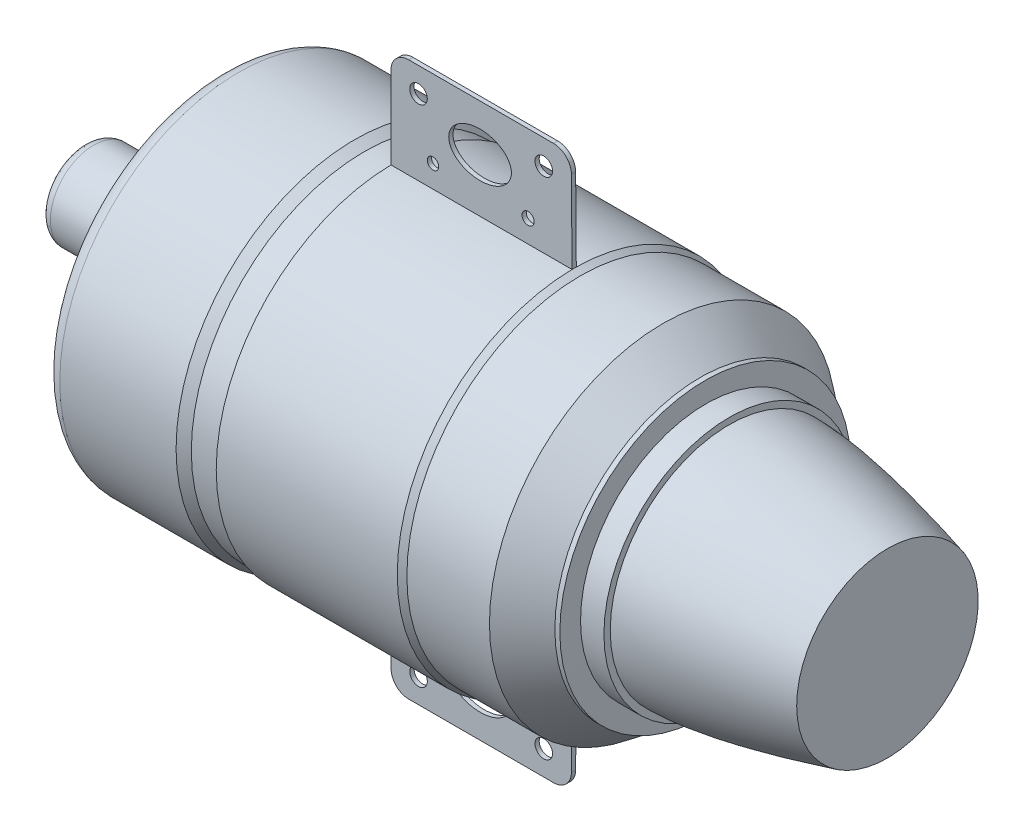
SolidWorks part; units mm, degrees
ref_plane "Front Plane" through (0, 0, 0) normal (0, 0, 1) x (1, 0, 0)
ref_plane "Top Plane" through (0, 0, 0) normal (0, 1, 0) x (1, 0, 0)
ref_plane "Right Plane" through (0, 0, 0) normal (1, 0, 0) x (0, 0, -1)
sketch "Sketch1" plane through (0, 0, 0) normal (0, 0, 1) x (1, 0, 0)
  line L0 (-26.7963, 0) -> (12.4273, 0) construction
  line L1 (1.0905, 5.1722) -> (9.4504, 5.1722)
  line L2 (9.4504, 5.1722) -> (9.4504, 0)
  line L3 (17.0937, 0) -> (17.0937, 18.9133)
  line L4 (19.2083, 21.3115) -> (33.0854, 21.3115)
  line L5 (33.0854, 21.3115) -> (34.2496, 20.6596)
  line L6 (34.2496, 20.6596) -> (37.6708, 20.6596)
  line L7 (59.2694, 21.1075) -> (60.0052, 20.6955)
  line L8 (60.0052, 20.6955) -> (69.8575, 20.6955)
  line L9 (69.8575, 20.6955) -> (74.3124, 17.3492)
  line L10 (74.3124, 17.3492) -> (74.9094, 17.3492)
  line L11 (74.9094, 17.3492) -> (74.9817, 14.9528)
  line L12 (74.9817, 14.9528) -> (77.7707, 14.9528)
  line L13 (77.7707, 14.9528) -> (77.7707, 14.1977)
  line L14 (96.6452, 0) -> (96.6452, 10.8275)
  line L15 (85.173, 14.1977) -> (70.5882, 14.1977) construction
  line L16 (0, 0) -> (0, -2.4925) construction
  line L17 (37.6708, 20.6596) -> (37.6708, 21.1075)
  line L18 (37.6708, 21.1075) -> (59.2694, 21.1075)
  line L19 (17.0937, 17.7576) -> (11.0147, 6.1199)
  line L20 (17.0937, 14.4568) -> (12.1234, 4.9415)
  line L21 (12.1234, 4.9415) -> (12.1234, 0)
  line L22 (37.6708, 21.1075) -> (37.6708, 30.916)
  line L23 (17.0937, 0) -> (96.6452, 0)
  line L24 (39.7842, 33.0294) -> (57.0627, 33.0294)
  line L25 (9.4504, 0) -> (0, 0)
  line L26 (59.1927, 30.916) -> (59.2694, 21.1075)
  line L27 (12.1234, 0) -> (9.4504, 0)
  line L28 (9.4504, 5.1722) -> (9.4504, 7.9511)
  line L29 (9.4504, 7.9511) -> (11.9713, 7.9511)
  line L30 (59.2694, 21.1075) -> (59.2694, 18.6791)
  line L31 (59.2694, 18.6791) -> (37.6708, 18.6791)
  line L32 (37.6708, 18.6791) -> (37.6708, 20.6596)
  arc A0 (17.0937, 18.9133) -> (19.2083, 21.3115) centre (19.511, 18.9133) cw
  arc A1 (0, 0) -> (1.0905, 5.1722) centre (12.8113, 0) cw
  arc A2 (9.4504, 5.1722) -> (11.0147, 6.1199) centre (9.4504, 6.9371) ccw
  arc A3 (37.6708, 30.916) -> (39.7842, 33.0294) centre (39.7842, 30.916) cw
  arc A4 (57.0627, 33.0294) -> (59.1927, 30.916) centre (57.0627, 30.8993) cw
  circle A5 centre (55.9165, 30.1262) radius 0.9796
  circle A6 centre (40.8958, 30.1262) radius 0.98
  circle A7 centre (42.6827, 23.7624) radius 0.6813
  circle A8 centre (54.0254, 23.7624) radius 0.7233
  ellipse E0 centre (48.297, 27.463) end of major axis (52.0357, 27.463) minor radius 2.6632
  spline S0 degree 2 poles (77.7707, 14.1977) (83.9678, 14.1977) (96.6452, 10.8275) knots 0 0 0 1 1 1
revolve "Revolve1" add sketch "Sketch1" angle 360 about L0 region at (4.898, 2.5349, 0) region at (53.424, 9.3335, 0) region at (48.4701, 19.8933, 0)
extrude "Boss-Extrude1" add sketch "Sketch1<4>" along normal mid plane 0.508 contours A4 L24 A3 L22 L18 L26 E0 A8 A7 A6 A5 | L32 L31 L30 L18 L17 | A6 | A5 region at (48.4701, 19.8933, 0) region at (37.9175, 26.0118, 0)
sketch "Sketch1<4>" plane through (0, 0, 0) normal (0, 0, 1) x (1, 0, 0) same geometry as "Sketch1"
extrude "Boss-Extrude2" add sketch "Sketch1<5>" along normal mid plane 2.54 contours A2 L2 L27 L21 L20 L3 L19 region at (12.7514, 7.2447, 0)
sketch "Sketch1<5>" plane through (0, 0, 0) normal (0, 0, 1) x (1, 0, 0) same geometry as "Sketch1"
revolve "Cut-Revolve1" cut sketch "Sketch1<6>" angle 360 about L0 region at (10.3968, 6.8036, 0)
sketch "Sketch1<6>" plane through (0, 0, 0) normal (0, 0, 1) x (1, 0, 0) same geometry as "Sketch1"
pattern_circular "CirPattern1" count 4 over 360 about axis through (-26.7963, 0, 0) along (1, 0, 0) of "Boss-Extrude2", "Cut-Revolve1"
mirror "Mirror1" about plane through (0, 0, 0) normal (0, 1, 0) of "Boss-Extrude1"
fillet "Fillet1" radius 1.27 1 edges at (1.0905, 0, 5.1722)
scale "Scale1" scale about centroid uniform scaling yes scale factor 2.276
sketch "Sketch2" plane through (0, 0, 0.5781) normal (0, 0, 1) x (1, 0, 0)
  line L0 (46.4059, 75.1749) -> (46.4059, 62.3363) construction
  line L1 (0, 0) -> (39.7086, 0)
  line L5 (21.9329, 70.3648) -> (21.9329, 48.0373)
  line L6 (21.9329, 48.0373) -> (71.0914, 48.0373)
  line L7 (71.0914, 48.0373) -> (71.0914, 48.0407)
  line L8 (71.0914, 48.0407) -> (70.9167, 70.3648)
  line L9 (66.0688, 75.1749) -> (26.743, 75.1749)
  line L14 (66.0688, 75.1749) -> (26.743, 75.1749)
  circle A0 centre (29.4059, 68.5) radius 2.3812
  circle A1 centre (63.4059, 68.5) radius 2.3812
  arc A2 (70.9167, 70.3648) -> (66.0688, 75.1749) centre (66.0688, 70.3269) ccw
  arc A3 (26.743, 75.1749) -> (21.9329, 70.3648) centre (26.743, 70.3648) ccw
  arc A4 (70.9167, 70.3648) -> (66.0688, 75.1749) centre (66.0688, 70.3269) ccw
  arc A5 (26.743, 75.1749) -> (21.9329, 70.3648) centre (26.743, 70.3648) ccw
  circle A6 centre (29.4059, -68.5) radius 2.3812
  circle A7 centre (63.4059, -68.5) radius 2.3812
  dimension "D2" = 4.7625
  dimension "D3" = 34
  dimension "D4" = 17
  dimension "D5" = 137
  dimension "D6" = 68.5
  dimension "D1" = 0
extrude "Cut-Extrude1" cut sketch "Sketch2" against normal through all contours A0 | A1 | A6 | A7 region at (29.4059, 68.5, 0.5781) region at (63.4059, 68.5, 0.5781) region at (29.4059, -68.5, 0.5781) region at (63.4059, -68.5, 0.5781)
ref_axis "Axis1" through (-74.8041, 0, 0) along (1, 0, 0)
equation "\"D4@Sketch2\"=\"D3@Sketch2\"/2"
equation "\"D6@Sketch2\"=\"D5@Sketch2\"/2"
equation "\"D2@Sketch2\"=6/32"
